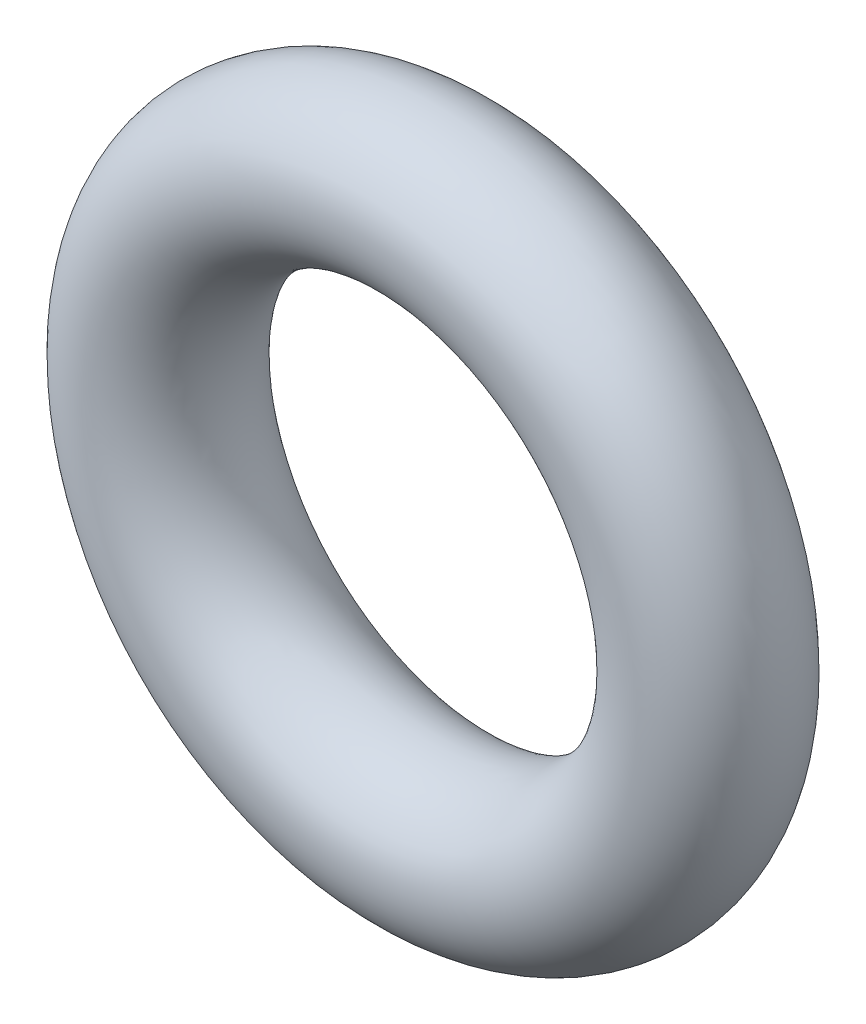
SolidWorks part; units mm, degrees
ref_plane "정면" through (0, 0, 0) normal (0, 0, 1) x (1, 0, 0)
ref_plane "윗면" through (0, 0, 0) normal (0, 1, 0) x (1, 0, 0)
ref_plane "우측면" through (0, 0, 0) normal (1, 0, 0) x (0, 0, -1)
ref_axis "기준축2" through (0, 0, 210) along (0, 0, -1)
ref_axis "기준축4" through (0, 55, 0) along (0, -1, 0)
sketch "스케치1" plane through (0, 0, 0) normal (1, 0, 0) x (0, 0, -1)
  line L0 (0, 55) -> (0, -55) construction
  line L1 (0, 0) -> (0, 1000) construction
  circle A0 centre (0, 35) radius 10
  dimension "D1" = 35
  dimension "D2" = 20
revolve "회전1" add sketch "스케치1" angle 360 about axis through (0, 0, 210) along (0, 0, -1)
